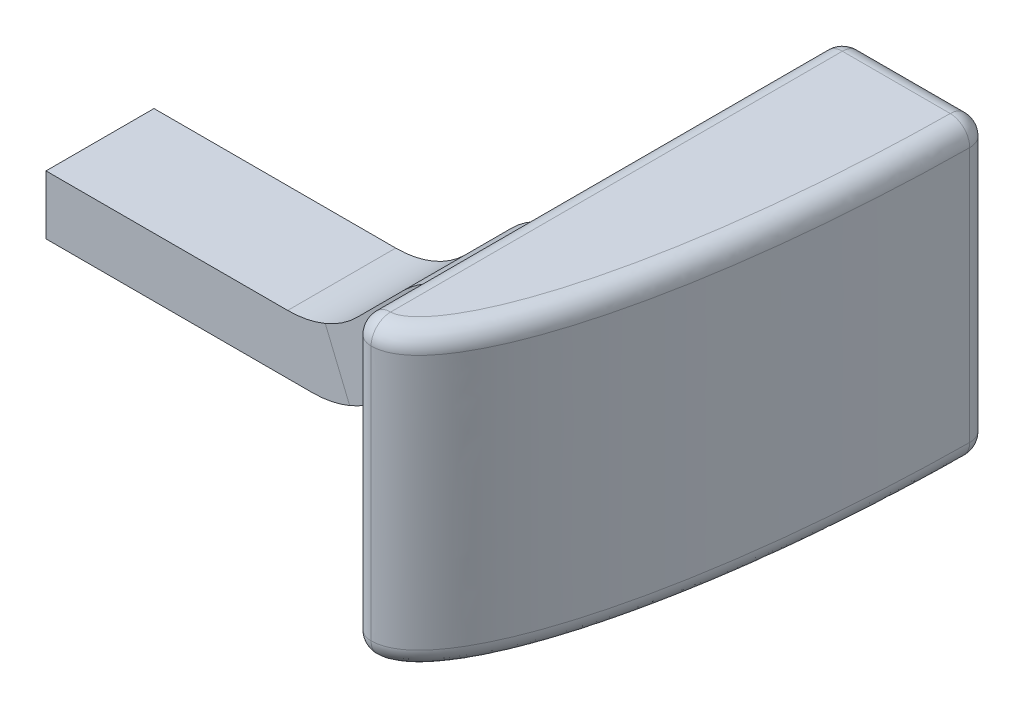
SolidWorks part; units mm, degrees
ref_plane "Front Plane" through (0, 0, 0) normal (0, 0, 1) x (1, 0, 0)
ref_plane "Top Plane" through (0, 0, 0) normal (0, 1, 0) x (1, 0, 0)
ref_plane "Right Plane" through (0, 0, 0) normal (1, 0, 0) x (0, 0, -1)
sketch "Sketch1" plane through (0, 0, 0) normal (1, 0, 0) x (0, 0, -1)
  line L1 (0, 0) -> (11, 0)
  line L2 (0, 0) -> (0, -6)
  line L3 (0, -6) -> (11, -6)
  line L4 (11, 0) -> (11, -6)
  dimension "D1" = 11
  dimension "D2" = 6
extrude "Boss-Extrude1" add sketch "Sketch1" along normal blind 20
ref_plane "Plane2" through (0, -3, 0) normal (0, 1, 0) x (1, 0, 0)
sketch3d "3DSketch3"
  line L0 (20, -3, -5.5) -> (30, -3, -5.5)
  line L1 (30, -3, -5.5) -> (40.6066, 7.6066, -5.5)
  line L2 (20, 0, -11) -> (20, 0, 0) construction
  line L3 (20, -6, -11) -> (20, 0, -11) construction
  line L4 (40.6066, 7.6066, -5.5) -> (50.6066, 7.6066, -5.5)
  dimension "D1" = 3
  dimension "D2" = 0
  dimension "D3" = 5.5
  dimension "D4" = 135
  dimension "D5" = 10
  dimension "D6" = 15
  dimension "D7" = 10
sketch "Sketch14" plane through (20, 0, 0) normal (1, 0, 0) x (0, 0, -1)
  line L1 (0, 0) -> (11, 0)
  line L2 (0, 0) -> (0, -6)
  line L3 (0, -6) -> (11, -6)
  line L4 (11, 0) -> (11, -6)
sweep "Sweep3" add profiles "Sketch14" path "3DSketch3"
fillet "Fillet1" radius 10 4 edges at (31.2426, -6, -5.5) (41.8492, 4.6066, -5.5) (39.364, 10.6066, -5.5) (28.7574, 0, -5.5)
sketch "Sketch16" plane through (50.6066, 0, 0) normal (1, 0, 0) x (0, 0, -1)
  line L1 (30.5, -7.3934) -> (-19.5, -7.3934)
  line L2 (30.5, -7.3934) -> (30.5, 22.6066)
  line L3 (30.5, 22.6066) -> (-19.5, 22.6066)
  line L4 (-19.5, -7.3934) -> (-19.5, 22.6066)
  line L9 (11, 10.6066) -> (0, 10.6066) construction
  line L10 (11, 4.6066) -> (11, 10.6066) construction
  point P5 (0, 0)
  dimension "D1" = 30
  dimension "D2" = 50
  dimension "D3" = 12
  dimension "D4" = 19.5
extrude "Boss-Extrude2" add sketch "Sketch16" along normal blind 15
fillet "Fillet2" radius 13 1 edges at (65.6066, 7.6066, 19.5) second distance 50 first distance on face at (58.1066, 7.6066, 19.5)
fillet "Fillet3" radius 2 13 edges at (50.6066, 7.6066, -11) (50.6066, 4.6066, -5.5) (50.6066, 7.6066, 0) (50.6066, 10.6066, -5.5) (50.6066, 7.6066, 19.5) (50.6066, -7.3934, -5.5) (50.6066, 22.6066, -5.5) (50.6066, 7.6066, -30.5)
